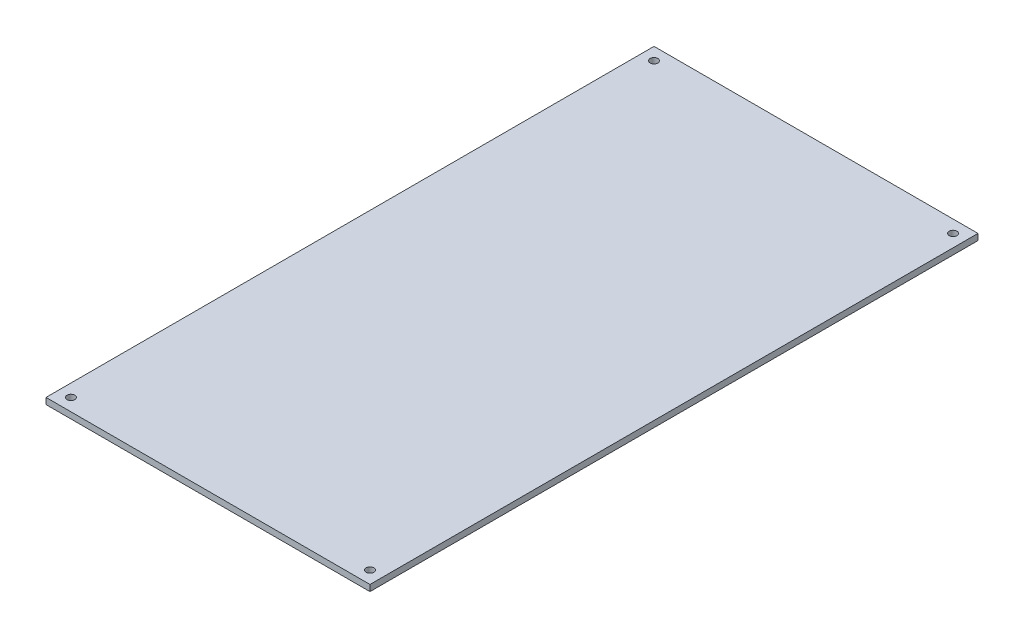
SolidWorks part; units mm, degrees
ref_plane "Front Plane" through (0, 0, 0) normal (0, 0, 1) x (1, 0, 0)
ref_plane "Top Plane" through (0, 0, 0) normal (0, 1, 0) x (1, 0, 0)
ref_plane "Right Plane" through (0, 0, 0) normal (1, 0, 0) x (0, 0, -1)
sketch "Sketch1" plane through (0, -91.8972, 0) normal (0, 1, 0) x (1, 0, 0)
  line L1 (-799.2, 626.1453) -> (-469, 626.1453)
  line L2 (-799.2, 626.1453) -> (-799.2, 6.4453)
  line L3 (-799.2, 6.4453) -> (-469, 6.4453)
  line L4 (-469, 626.1453) -> (-469, 6.4453)
  circle A0 centre (-786.5, 19.1453) radius 3.1293 construction
  circle A1 centre (-481.7, 19.1453) radius 3.9687 construction
  circle A2 centre (-481.7, 19.1453) radius 3.1293 construction
  circle A3 centre (-786.5, 613.4453) radius 3.1293 construction
  circle A4 centre (-481.7, 613.4453) radius 3.9687 construction
  circle A5 centre (-481.7, 613.4453) radius 3.9687
  circle A6 centre (-786.5, 613.4453) radius 3.9687 construction
  circle A7 centre (-786.5, 613.4453) radius 3.9687
  circle A8 centre (-786.5, 19.1453) radius 3.9687 construction
  circle A9 centre (-786.5, 19.1453) radius 3.9687
  circle A10 centre (-481.7, 19.1453) radius 3.9688
extrude "Boss-Extrude1" add sketch "Sketch1" along normal blind 6.35
